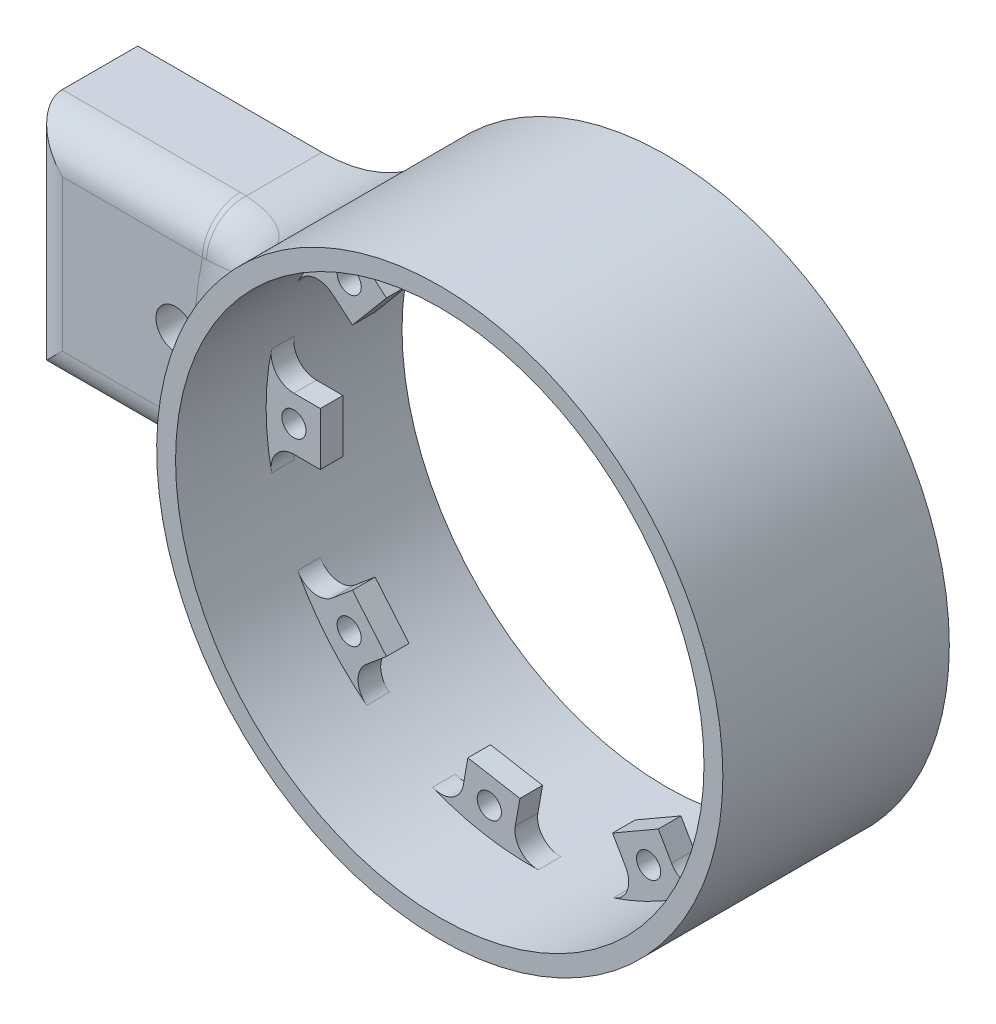
SolidWorks part; units mm, degrees
ref_plane "Plan de face" through (0, 0, 0) normal (0, 0, 1) x (1, 0, 0)
ref_plane "Plan de dessus" through (0, 0, 0) normal (0, 1, 0) x (1, 0, 0)
ref_plane "Plan de droite" through (0, 0, 0) normal (1, 0, 0) x (0, 0, -1)
sketch "Esquisse5" plane through (0, 0, 0) normal (0, 0, 1) x (1, 0, 0)
  line L0 (-1000, 0) -> (49000, 0) construction
  line L1 (-45.6207, 15) -> (-70, 15)
  line L2 (-70, 15) -> (-70, -15)
  line L3 (-45.6207, -15) -> (-70, -15)
  circle A0 centre (0, 0) radius 35
  arc A1 (-29.7526, -22.8261) -> (-29.7526, 22.8261) centre (0, 0) ccw
  arc A2 (-45.6207, 15) -> (-29.7526, 22.8261) centre (-45.6207, 35) ccw
  arc A3 (-45.6207, -15) -> (-29.7526, -22.8261) centre (-45.6207, -35) cw
  point P14 (-70, 0)
  dimension "D1" = 70
  dimension "D2" = 75
  dimension "D5" = 20
  dimension "D3" = 15
  dimension "D4" = 70
extrude "Boss.-Extru.4" add sketch "Esquisse5" along normal blind 15
sketch "Esquisse8" plane through (0, 0, 15) normal (0, 0, 1) x (1, 0, 0)
  circle A0 centre (0, 0) radius 35
  circle A1 centre (0, 0) radius 37.5
  circle A2 centre (0, 0) radius 35 construction
  arc A3 (-29.7526, -22.8261) -> (-29.7526, 22.8261) centre (0, 0) ccw construction
extrude "Boss.-Extru.7" add sketch "Esquisse8" along normal blind 15
ref_plane "Plan1" through (0, 0, 15) normal (0, 0, 1) x (1, 0, 0)
sketch "Esquisse15" plane through (0, 0, 15) normal (0, 0, 1) x (1, 0, 0)
  line L0 (-19.0651, 20.5664) -> (-21.7526, 22.8215)
  line L1 (-27.8246, -3.5) -> (-31.3329, -3.5)
  line L2 (-27.8246, -3.5) -> (-27.8246, 3.5)
  line L3 (-27.8246, 3.5) -> (-31.3329, 3.5)
  line L5 (-27.8246, -3.5) -> (-34.8246, 3.5) construction
  line L6 (-27.8246, 3.5) -> (-34.8246, -3.5) construction
  line L7 (-23.5646, 15.2041) -> (-19.0651, 20.5664)
  line L8 (-23.5646, 15.2041) -> (-26.2521, 17.4592)
  line L9 (-1.3849, 28.0096) -> (-1.9941, 31.4646)
  line L10 (-8.2785, 26.7941) -> (-1.3849, 28.0096)
  line L11 (-8.2785, 26.7941) -> (-8.8877, 30.2491)
  line L12 (16.9434, 22.3468) -> (18.6975, 25.3851)
  line L13 (10.8812, 25.8468) -> (16.9434, 22.3468)
  line L14 (10.8812, 25.8468) -> (12.6354, 28.8851)
  line L15 (27.3436, 6.2276) -> (30.6404, 7.4276)
  line L16 (24.9495, 12.8055) -> (27.3436, 6.2276)
  line L17 (24.9495, 12.8055) -> (28.2462, 14.0054)
  line L18 (24.9495, -12.8055) -> (28.2462, -14.0054)
  line L19 (27.3436, -6.2276) -> (24.9495, -12.8055)
  line L20 (27.3436, -6.2276) -> (30.6404, -7.4276)
  line L21 (10.8812, -25.8468) -> (12.6354, -28.8851)
  line L22 (16.9434, -22.3468) -> (10.8812, -25.8468)
  line L23 (16.9434, -22.3468) -> (18.6975, -25.3851)
  line L24 (-8.2785, -26.7941) -> (-8.8877, -30.2491)
  line L25 (-1.3849, -28.0096) -> (-8.2785, -26.7941)
  line L26 (-1.3849, -28.0096) -> (-1.9941, -31.4646)
  line L27 (-23.5646, -15.2041) -> (-26.2521, -17.4592)
  line L28 (-19.0651, -20.5664) -> (-23.5646, -15.2041)
  line L29 (-19.0651, -20.5664) -> (-21.7526, -22.8215)
  arc A0 (-34.2703, -7.1094) -> (-30.8224, -16.5825) centre (0, 0) ccw
  circle A1 centre (0, 0) radius 35 construction
  circle A2 centre (0, 0) radius 37.5
  circle A3 centre (0, 0) radius 37.5 construction
  circle A4 centre (-31.3246, 0) radius 1.6
  arc A5 (-31.3329, -3.5) -> (-34.2703, -7.1094) centre (-31.3329, -6.5) ccw
  arc A6 (-31.3329, 3.5) -> (-34.2703, 7.1094) centre (-31.3329, 6.5) cw
  arc A7 (-21.7526, 22.8215) -> (-21.6828, 27.4747) centre (-19.8243, 25.1197) cw
  arc A8 (-26.2521, 17.4592) -> (-30.8224, 16.5825) centre (-28.1805, 15.1611) ccw
  circle A9 centre (-23.996, 20.135) radius 1.6
  arc A10 (-1.9941, 31.4646) -> (1.0504, 34.9842) centre (0.9604, 31.9856) cw
  arc A11 (-8.8877, 30.2491) -> (-12.9524, 32.5152) centre (-11.8421, 29.7282) ccw
  circle A12 centre (-5.4395, 30.8487) radius 1.6
  arc A13 (18.6975, 25.3851) -> (23.2921, 26.1243) centre (21.2956, 23.8851) cw
  arc A14 (12.6354, 28.8851) -> (10.9783, 33.2337) centre (10.0373, 30.3851) ccw
  circle A15 centre (15.6623, 27.1279) radius 1.6
  arc A16 (30.6404, 7.4276) -> (34.6351, 5.0405) centre (31.6664, 4.6085) cw
  arc A17 (28.2462, 14.0054) -> (29.772, 18.4018) centre (27.2202, 16.8245) ccw
  circle A18 centre (29.4355, 10.7136) radius 1.6
  arc A19 (28.2462, -14.0054) -> (29.772, -18.4018) centre (27.2202, -16.8245) cw
  arc A20 (30.6404, -7.4276) -> (34.6351, -5.0405) centre (31.6664, -4.6085) ccw
  circle A21 centre (29.4355, -10.7136) radius 1.6
  arc A22 (12.6354, -28.8851) -> (10.9783, -33.2337) centre (10.0373, -30.3851) cw
  arc A23 (18.6975, -25.3851) -> (23.2921, -26.1243) centre (21.2956, -23.8851) ccw
  circle A24 centre (15.6623, -27.1279) radius 1.6
  arc A25 (-8.8877, -30.2491) -> (-12.9524, -32.5152) centre (-11.8421, -29.7282) cw
  arc A26 (-1.9941, -31.4646) -> (1.0504, -34.9842) centre (0.9604, -31.9856) ccw
  circle A27 centre (-5.4395, -30.8487) radius 1.6
  arc A28 (-26.2521, -17.4592) -> (-30.8224, -16.5825) centre (-28.1805, -15.1611) cw
  arc A29 (-21.7526, -22.8215) -> (-21.6828, -27.4747) centre (-19.8243, -25.1197) ccw
  circle A30 centre (-23.996, -20.135) radius 1.6
  arc A31 (-30.8224, 16.5825) -> (-34.2703, 7.1094) centre (0, 0) ccw
  arc A32 (-12.9524, 32.5152) -> (-21.6828, 27.4747) centre (0, 0) ccw
  arc A33 (10.9783, 33.2337) -> (1.0504, 34.9842) centre (0, 0) ccw
  arc A34 (29.772, 18.4018) -> (23.2921, 26.1243) centre (0, 0) ccw
  arc A35 (34.6351, -5.0405) -> (34.6351, 5.0405) centre (0, 0) ccw
  arc A36 (23.2921, -26.1243) -> (29.772, -18.4018) centre (0, 0) ccw
  arc A37 (1.0504, -34.9842) -> (10.9783, -33.2337) centre (0, 0) ccw
  arc A38 (-21.6828, -27.4747) -> (-12.9524, -32.5152) centre (0, 0) ccw
  point P5 (-31.3246, 0)
  point P103 (0, 0)
  dimension "D3" = 3.2
  dimension "D5" = 3
  dimension "D1" = 7
  dimension "D2" = 7
  dimension "D4" = 3.5
  dimension "D6" = 9
extrude "Boss.-Extru.8" add sketch "Esquisse15" along normal blind 3
fillet "Congé3" radius 10 1 edges at (-37.5, 0, 15)
fillet "Congé4" radius 5 7 edges at (-45.3438, 15.0019, 15) (-45.3438, -15.0019, 15) (-36.9031, 16.9999, 17.733) (-57.8104, 15, 15) (-70, 0, 15) (-57.8104, -15, 15) (-36.9031, -16.9999, 17.733)
sketch "Esquisse12" plane through (-70, 0, 0) normal (-1, 0, 0) x (0, 0, 1)
  line L5 (0, 10) -> (10, 10) construction
  line L8 (0, 15) -> (0, -15) construction
  line L9 (10, 10) -> (10, -10) construction
  line L10 (-1000, 0) -> (49000, 0) construction
  line L11 (0, -10) -> (10, -10) construction
  line L12 (10, 15) -> (0, 15) construction
  line L14 (0, 10) -> (0, -10) construction
  line L15 (-0.2, 10.2) -> (10.2, 10.2)
  line L16 (10.2, 10.2) -> (10.2, -10.2)
  line L17 (-0.2, -10.2) -> (10.2, -10.2)
  line L18 (-0.2, 10.2) -> (-0.2, -10.2)
  line L20 (15, -10) -> (15, 10) construction
  point P9 (10, 0)
  dimension "D1" = 5
  dimension "D2" = 5
  dimension "D3" = 0.2
extrude "Enlèv. mat.-Extru.2" cut sketch "Esquisse12" against normal blind 30
sketch "Esquisse13" plane through (0, 0, 15) normal (0, 0, 1) x (1, 0, 0)
  line L0 (-69.996, -10.2) -> (-69.996, 10.2) construction
  circle A0 centre (-49.996, 0) radius 2.6
  dimension "D1" = 5.2
  dimension "D2" = 20
extrude "Enlèv. mat.-Extru.3" cut sketch "Esquisse13" against normal up to next and the other way through all
